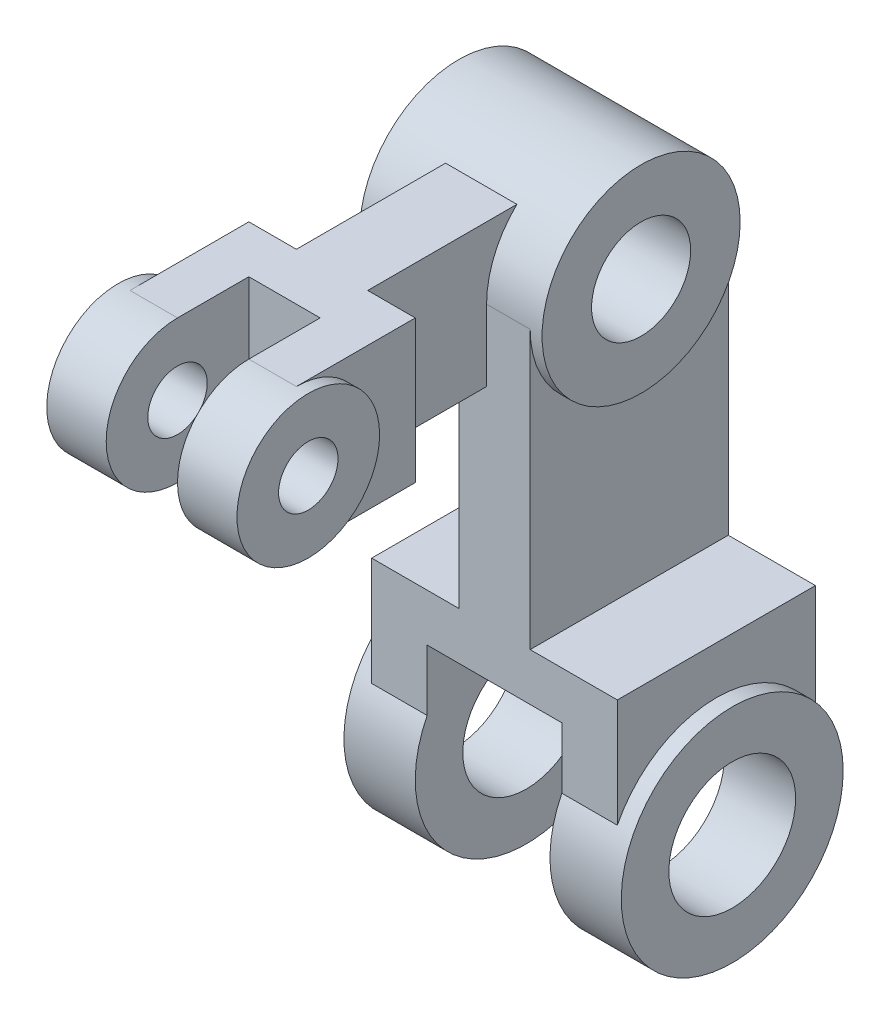
SolidWorks part; units mm, degrees
ref_plane "Front Plane" through (0, 0, 0) normal (0, 0, 1) x (1, 0, 0)
ref_plane "Top Plane" through (0, 0, 0) normal (0, 1, 0) x (1, 0, 0)
ref_plane "Right Plane" through (0, 0, 0) normal (1, 0, 0) x (0, 0, -1)
sketch "Sketch1" plane through (0, 0, 0) normal (1, 0, 0) x (0, 0, -1)
  circle A0 centre (0, 0) radius 25
  circle A1 centre (0, 0) radius 12.5
  dimension "D1" = 25
  dimension "D2" = 50
extrude "Boss-Extrude1" add sketch "Sketch1" along normal mid plane 46
sketch "Sketch4" plane through (0, 0, 0) normal (1, 0, 0) x (0, 0, -1)
  line L0 (-25, 0) -> (-25, -70)
  line L1 (-25, -70) -> (25, -70)
  line L2 (25, -70) -> (25, 0)
  circle A0 centre (0, 0) radius 25 construction
  arc A1 (-25, 0) -> (25, 0) centre (0, 0) ccw
  dimension "D1" = 70
extrude "Boss-Extrude3" add sketch "Sketch4" against normal blind 18 from offset 20
ref_plane "Plane1" through (11, 0, 0) normal (1, 0, 0) x (0, 0, -1)
sketch "Sketch5" plane through (11, 0, 0) normal (1, 0, 0) x (0, 0, -1)
  line L0 (-25, -70) -> (-25, -97.3905)
  line L1 (25, -70) -> (25, -97.3905)
  line L2 (0, 0) -> (0, -110) construction
  line L3 (-25, -70) -> (25, -70)
  circle A0 centre (0, -110) radius 28
  circle A1 centre (0, -110) radius 16
  dimension "D1" = 32
  dimension "D2" = 56
  dimension "D3" = 110
extrude "Boss-Extrude4" add sketch "Sketch5" along normal mid plane 70 separate body contours A0 A1 region at (11, -82.792, 0)
extrude "Boss-Extrude5" add sketch "Sketch5<4>" along normal mid plane 62 contours L2 L3 L0 A0 | L3 L2 A0 L1 region at (11, -78.7513, 14.2794) region at (11, -78.7513, -14.2794)
sketch "Sketch5<4>" plane through (11, 0, 0) normal (1, 0, 0) x (0, 0, -1) same geometry as "Sketch5"
sketch "Sketch6" plane through (0, 0, 25) normal (0, 0, 1) x (1, 0, 0)
  line L0 (42, -70) -> (20, -70) construction
  line L1 (-6, -82) -> (28, -82)
  line L2 (-6, -82) -> (-6, -152)
  line L3 (-6, -152) -> (28, -152)
  line L4 (28, -82) -> (28, -152)
  line L5 (46, -138) -> (46, -82) construction
  dimension "D1" = 34
  dimension "D2" = 12
  dimension "D3" = 18
  dimension "D4" = 70
extrude "Cut-Extrude2" cut sketch "Sketch6" against normal through all both and the other way through all contours L2 L3 L4 L1
sketch "Sketch8" plane through (0, 0, 0) normal (1, 0, 0) x (0, 0, -1)
  circle A0 centre (-85, 0) radius 18
  circle A1 centre (-85, 0) radius 7.5
  dimension "D1" = 36
  dimension "D2" = 15
  dimension "D3" = 85
extrude "Boss-Extrude6" add sketch "Sketch8" along normal mid plane 48 separate body
sketch "Sketch9" plane through (0, 0, 0) normal (1, 0, 0) x (0, 0, -1)
  line L0 (-85, 18) -> (-17.3494, 18)
  line L1 (-85, -18) -> (-25, -18)
  line L2 (-25, 0) -> (-25, -70) construction
  line L3 (-25, -18) -> (-25, 0)
  line L4 (-55, 18) -> (-55, -18)
  circle A0 centre (-85, 0) radius 18 construction
  arc A1 (-85, -18) -> (-85, 18) centre (-85, 0) ccw
  circle A2 centre (0, 0) radius 25 construction
  arc A3 (-17.3494, 18) -> (-25, 0) centre (0, 0) ccw
  dimension "D1" = 30
extrude "Boss-Extrude7" add sketch "Sketch9" along normal mid plane 42 contours A1 L1 L4 L0 region at (0, 0, 63.4402)
extrude "Boss-Extrude8" add sketch "Sketch9<3>" along normal mid plane 18 contours A3 L0 L4 L1 L3 region at (0, 0.5188, 39.3456)
sketch "Sketch9<3>" plane through (0, 0, 0) normal (1, 0, 0) x (0, 0, -1) same geometry as "Sketch9"
sketch "Sketch10" plane through (0, 18, 0) normal (0, 1, 0) x (1, 0, 0)
  line L0 (24, -103) -> (24, -67) construction
  line L1 (-9, -67) -> (9, -67)
  line L2 (-9, -67) -> (-9, -117)
  line L3 (-9, -117) -> (9, -117)
  line L4 (9, -67) -> (9, -117)
  line L5 (-9, -67) -> (9, -117) construction
  line L6 (-9, -117) -> (9, -67) construction
  line L7 (-9, -55) -> (-21, -55) construction
  point P0 (0, -92)
  dimension "D1" = 18
  dimension "D2" = 15
  dimension "D3" = 12
  dimension "D4" = 50
extrude "Cut-Extrude4" cut sketch "Sketch10" against normal through all both and the other way through all contours L2 L3 L4 L1
